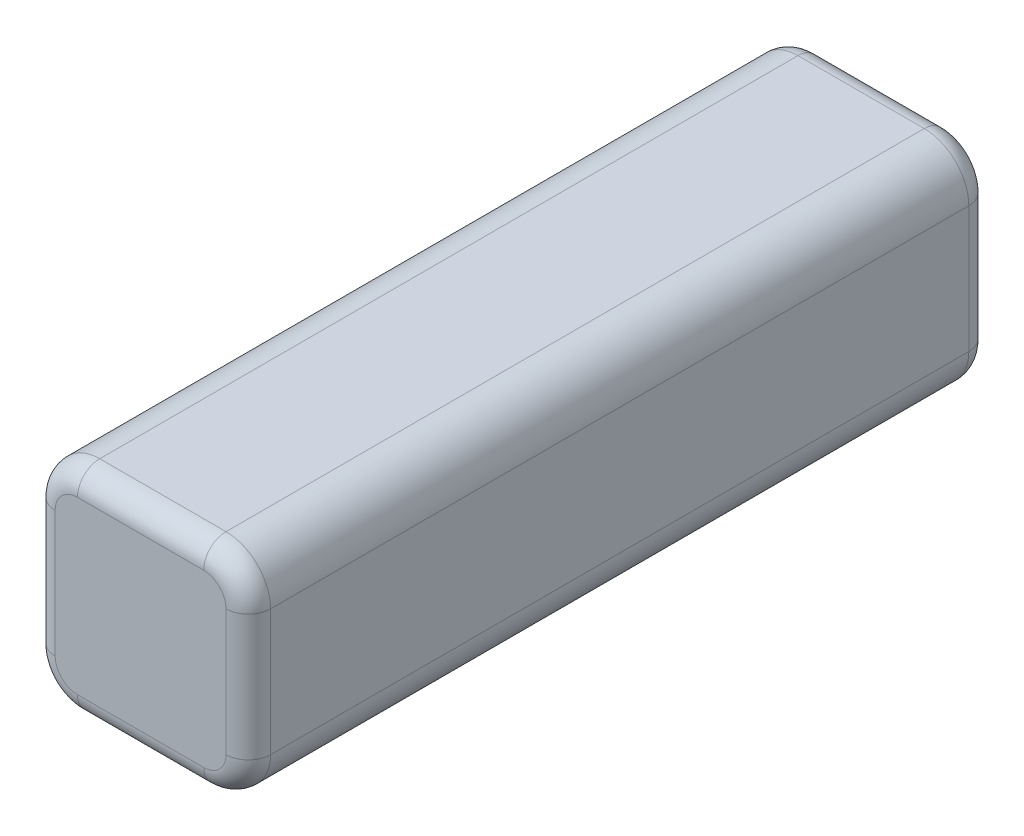
SolidWorks part; units mm, degrees
ref_plane "Plano frontal" through (0, 0, 0) normal (0, 0, 1) x (1, 0, 0)
ref_plane "Plano superior" through (0, 0, 0) normal (0, 1, 0) x (1, 0, 0)
ref_plane "Plano direito" through (0, 0, 0) normal (1, 0, 0) x (0, 0, -1)
sketch "Esboço1" plane through (0, 0, 0) normal (0, 0, 1) x (1, 0, 0)
  line L21 (-1.45, -0.85) -> (-1.45, 0.85)
  line L22 (-0.85, 1.45) -> (0.85, 1.45)
  line L23 (1.45, -0.85) -> (1.45, 0.85)
  line L24 (-0.85, -1.45) -> (0.85, -1.45)
  arc A22 (-1.45, 0.85) -> (-0.85, 1.45) centre (-0.85, 0.85) cw
  arc A23 (0.85, 1.45) -> (1.45, 0.85) centre (0.85, 0.85) cw
  arc A24 (0.85, -1.45) -> (1.45, -0.85) centre (0.85, -0.85) ccw
  arc A25 (-0.85, -1.45) -> (-1.45, -0.85) centre (-0.85, -0.85) cw
extrude "Ressalto-extrusão1" add sketch "Esboço1" along normal blind 10
fillet "Filete1" radius 0.3 16 edges at (0, 1.45, 0) (0, 1.45, 10) (0, -1.45, 0) (1.2743, -1.2743, 0) (1.45, 0, 0) (1.2743, 1.2743, 0) (-1.2743, 1.2743, 0) (-1.45, 0, 0) (-1.2743, -1.2743, 0) (-1.45, 0, 10) (-1.2743, 1.2743, 10) (1.2743, 1.2743, 10) (1.45, 0, 10) (1.2743, -1.2743, 10) (0, -1.45, 10) (-1.2743, -1.2743, 10)
sketch "Esboço2" plane through (0, 0, 0) normal (0, 0, -1) x (-1, 0, 0)
  line L0 (-1.45, 0) -> (1.45, 0) construction
  line L1 (-1.45, -0.85) -> (-1.45, 0.85) construction
  line L2 (1.45, 0.85) -> (1.45, -0.85) construction
  line L6 (-0.85, 1.45) -> (0.85, 1.45) construction
  line L7 (0, 1.45) -> (0, -1.45) construction
  line L9 (0.85, -1.45) -> (-0.85, -1.45) construction
